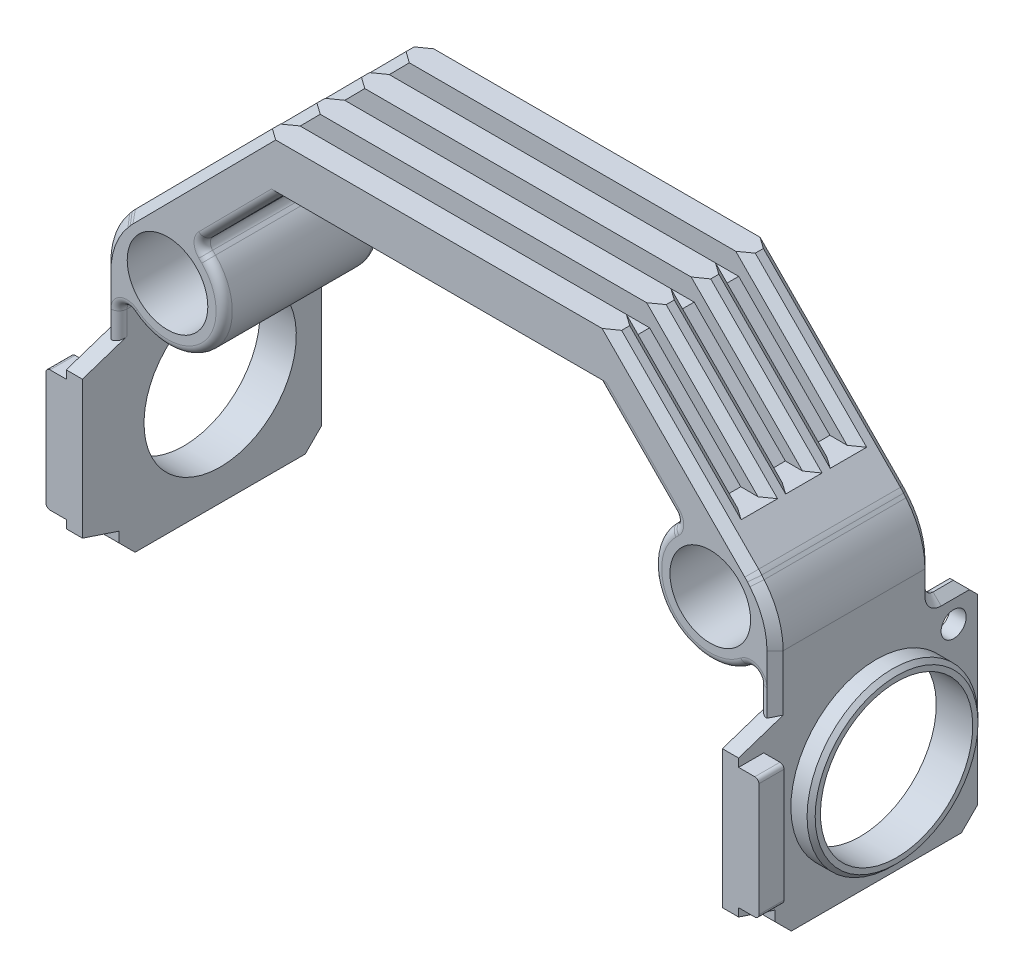
SolidWorks part; units mm, degrees
ref_plane "前视基准面" through (0, 0, 0) normal (0, 0, 1) x (1, 0, 0)
ref_plane "上视基准面" through (0, 0, 0) normal (0, 1, 0) x (1, 0, 0)
ref_plane "右视基准面" through (0, 0, 0) normal (1, 0, 0) x (0, 0, -1)
sketch "草图1" plane through (0, 0, 0) normal (0, 0, 1) x (1, 0, 0)
  circle A0 centre (-33.5, 0) radius 4.975
  circle A1 centre (-33.5, 0) radius 7
  point P4 (17.6304, -1.0507)
  dimension "D1" = 9.95
  dimension "D2" = 14
  dimension "D3" = 33.5
extrude "凸台-拉伸1" add sketch "草图1" along normal mid plane 25
sketch "草图3" plane through (0, 0, 0) normal (0, 0, 1) x (1, 0, 0)
  line L0 (-41.5, 1.356) -> (-41.5, -36.644)
  line L1 (-41.5, -36.644) -> (-39.5, -36.644)
  line L2 (-39.5, -36.644) -> (-39.5, -3.6056)
  line L3 (-41.5, 1.356) -> (-38.8623, 4.4995)
  circle A4 centre (-33.5, 0) radius 7 construction
  arc A5 (-38.8623, 4.4995) -> (-39.5, -3.6056) centre (-33.5, 0) ccw
  point P0 (-8, 1.7621)
  point P13 (-8, 0.2923)
  dimension "D1" = 8
  dimension "D2" = 2
  dimension "D3" = 38
  dimension "D4" = 40
extrude "凸台-拉伸2" add sketch "草图3" along normal mid plane 25
sketch "草图4" plane through (-41.5, 0, 0) normal (-1, 0, 0) x (0, 0, 1)
  circle A0 centre (0, -19.5) radius 9.4
  point P2 (0, 0)
  dimension "D1" = 18.8
  dimension "D2" = 19.5
extrude "切除-拉伸1" cut sketch "草图4" against normal through all
sketch "草图5" plane through (-41.5, 0, 0) normal (-1, 0, 0) x (0, 0, 1)
  circle A0 centre (0, -19.5) radius 10.55
  circle A1 centre (0, -19.5) radius 9.4
  circle A2 centre (0, -19.5) radius 9.4 construction
  dimension "D1" = 21.1
extrude "凸台-拉伸5" add sketch "草图5" along normal blind 2.5
chamfer "倒角3" distance 0.5 angle 45 1 edges at (-44, -30.05, 0)
sketch "草图6" plane through (-41.5, 0, 0) normal (-1, 0, 0) x (0, 0, 1)
  line L0 (12.5, -9.5) -> (17, -11)
  line L1 (12.5, 1.356) -> (12.5, -36.644) construction
  line L2 (17, -11) -> (17, -28)
  line L3 (17, -28) -> (12.5, -29.5)
  line L4 (12.5, -29.5) -> (12.5, -9.5)
  line L5 (0, -19.5) -> (17, -19.5) construction
  point P9 (12.5, -11)
  point P10 (12.5, -9.3792)
  point P11 (16.8715, -10.7591)
  point P12 (12.5, -32.9527)
  point P13 (12.5, -7.1943)
  dimension "D1" = 17
  dimension "D2" = 20
  dimension "D3" = 4.5
extrude "凸台-拉伸6" add sketch "草图6" against normal blind 2
sketch "草图7" plane through (-41.5, 0, 0) normal (-1, 0, 0) x (0, 0, 1)
  line L0 (17, -28) -> (17, -11) construction
  line L1 (13.9, -12) -> (17, -12)
  line L2 (13.9, -12) -> (13.9, -27)
  line L3 (13.9, -27) -> (17, -27)
  line L4 (17, -12) -> (17, -27)
  point P6 (17, -19.5)
  dimension "D1" = 15
  dimension "D2" = 3.1
extrude "凸台-拉伸7" add sketch "草图7" along normal blind 2.5
fillet "圆角1" radius 0.5 2 edges at (-44, -12, 15.45) (-44, -27, 15.45)
fillet "圆角2" radius 10 1 edges at (-41.5, 1.356, 0)
fillet "圆角3" radius 1 1 edges at (-39.5, -3.6056, 0)
sketch "草图8" plane through (0, 0, -12.5) normal (0, 0, -1) x (-1, 0, 0)
  line L0 (41.5, -2.2837) -> (41.5, -36.644) construction
  line L1 (41.5, -2.2837) -> (41.5, -6.245)
  line L2 (39.5, -6.245) -> (41.5, -6.245)
  line L3 (38.8623, 4.4995) -> (39.1604, 4.1442) construction
  line L4 (38.8623, 4.4995) -> (39.1604, 4.1442)
  arc A0 (38.8623, 4.4995) -> (37.875, -5.4644) centre (33.5, 0) ccw
  arc A1 (41.5, -2.2837) -> (39.1604, 4.1442) centre (31.5, -2.2837) ccw construction
  arc A2 (39.5, -6.245) -> (37.875, -5.4644) centre (38.5, -6.245) ccw construction
  arc A3 (41.5, -2.2837) -> (39.1604, 4.1442) centre (31.5, -2.2837) ccw
  arc A4 (39.5, -6.245) -> (37.875, -5.4644) centre (38.5, -6.245) ccw
  circle A5 centre (33.5, 0) radius 4.975 construction
extrude "切除-拉伸2" cut sketch "草图8" against normal blind 5.5
sketch "草图9" plane through (-41.5, 0, 0) normal (-1, 0, 0) x (0, 0, 1)
  line L0 (0, -19.5) -> (-12.5, -19.5) construction
  line L1 (-12.5, -6.245) -> (-12.5, -36.644) construction
  line L2 (-7, -6.245) -> (-12.5, -6.245) construction
  line L3 (-7, -6.245) -> (-12.5, -6.245) construction
  line L4 (-12.5, -32.755) -> (12.5, -32.755)
  line L5 (12.5, -29.5) -> (12.5, -36.644) construction
  line L6 (-12.5, -32.755) -> (-12.5, -36.644)
  line L7 (-12.5, -36.644) -> (12.5, -36.644)
  line L8 (12.5, -36.644) -> (12.5, -32.755)
extrude "切除-拉伸3" cut sketch "草图9" against normal through all
fillet "圆角4" radius 1 1 edges at (-40.5, -6.245, -7)
mirror "镜向2" about plane through (0, 0, 0) normal (1, 0, 0) of bodies 109
sketch "草图10" plane through (0, 0, -7) normal (0, 0, -1) x (-1, 0, 0)
  line L0 (-38.4723, 4.9271) -> (-21.5545, 22)
  line L1 (-21.5545, 22) -> (21.5545, 22)
  line L2 (21.5545, 22) -> (38.4723, 4.9271)
  line L3 (-31.1793, 6.6041) -> (-19.887, 18)
  line L4 (-19.887, 18) -> (19.887, 18)
  line L5 (19.887, 18) -> (31.1793, 6.6041)
  arc A1 (-37.875, -5.4644) -> (-38.8623, 4.4995) centre (-33.5, 0) ccw construction
  arc A2 (38.8623, 4.4995) -> (37.875, -5.4644) centre (33.5, 0) ccw construction
  arc A3 (38.4723, 4.9271) -> (31.1793, 6.6041) centre (33.5, 0) ccw
  arc A4 (-31.1793, 6.6041) -> (-38.4723, 4.9271) centre (-33.5, 0) ccw
  circle A5 centre (33.5, 0) radius 4.975 construction
  point P10 (0, 22)
  point P16 (0, 18)
  point P17 (-21.6674, 10.2957)
  dimension "D1" = 4
  dimension "D4" = 22
  dimension "D2" = 4
  dimension "D3" = 134.739
extrude "凸台-拉伸8" add sketch "草图10" against normal blind 3
pattern_linear "阵列(线性)1" count 4 spacing 5.5 along (0, 0, 1) of "凸台-拉伸8"
sketch "草图11" plane through (0, 0, -7) normal (0, 0, -1) x (-1, 0, 0)
  line L1 (-21.5545, 22) -> (-38.4723, 4.9271) construction
  line L2 (-38.4723, 4.9271) -> (-33.5452, 9.8994)
  line L3 (-33.5452, 9.8994) -> (-28.5729, 4.9723)
  line L4 (-38.4723, 4.9271) -> (-31.1793, 6.6041)
  arc A0 (-37.875, -5.4644) -> (-31.1793, 6.6041) centre (-33.5, 0) ccw construction
  arc A1 (-28.5729, 4.9723) -> (-31.1793, 6.6041) centre (-33.5, 0) ccw
  point P10 (-28.8352, 5.2191)
extrude "凸台-拉伸9" add sketch "草图11" against normal up to surface (19.5 mm away)
mirror "镜向3" about plane through (0, 0, 0) normal (1, 0, 0) of "凸台-拉伸9"
sketch "草图12" plane through (0, 0, -7) normal (0, 0, -1) x (-1, 0, 0)
  line L0 (-29.6384, 6.0281) -> (-19.2616, 16.5)
  line L1 (-28.5729, 4.9723) -> (-30.7039, 7.0839) construction
  line L2 (-19.2616, 16.5) -> (19.2616, 16.5)
  line L3 (19.2616, 16.5) -> (29.6384, 6.0281)
  line L4 (28.5729, 4.9723) -> (30.7039, 7.0839) construction
  line L6 (-19.887, 18) -> (19.887, 18) construction
  line L7 (-29.6384, 6.0281) -> (-31.7694, 8.1397)
  line L8 (-31.7694, 8.1397) -> (-20.5123, 19.5)
  line L9 (-20.5123, 19.5) -> (20.5123, 19.5)
  line L10 (20.5123, 19.5) -> (31.7694, 8.1397)
  line L11 (31.7694, 8.1397) -> (29.6384, 6.0281)
  dimension "D1" = 1.5
  dimension "D2" = 3
  dimension "D3" = 3
extrude "凸台-拉伸10" add sketch "草图12" against normal blind 19.5
chamfer "倒角5" distance 2 angle 45 6 edges at (-40.5, -6.245, -12.5) (-40.5, -32.755, -12.5) (-40.5, -32.755, 12.5) (40.5, -32.755, 12.5) (40.5, -6.245, -12.5) (40.5, -32.755, -12.5)
chamfer "倒角4" distance 1 angle 45 36 edges at (-40.8969, 1.1365, -7) (-38.6717, 4.7173, -7) (-39.0114, 4.3219, -7) (-39.0114, 4.3219, 12.5) (-41.5, -3.7643, -7) (-41.5, -6.245, -9.25) (-41.5, -5.9521, -7.2929) (27.5498, 15.9497, -4) (-30.0134, 13.4636, -7) (30.0134, 13.4636, -7) (38.6717, 4.7173, -7) (39.0114, 4.3219, -7) (39.0114, 4.3219, 12.5) (40.8969, 1.1365, 12.5) (40.8969, 1.1365, -7) (41.5, -3.7643, -7) (41.5, -5.8918, 12.5) (41.5, -6.245, -9.25) (41.5, -5.9521, -7.2929) (27.5498, 15.9497, 1.5) (27.5498, 15.9497, -1.5) (27.5498, 15.9497, 7) (27.5498, 15.9497, 4) (38.6717, 4.7173, 12.5) (-38.6717, 4.7173, 12.5) (30.0134, 13.4636, 12.5) (-30.0134, 13.4636, 12.5) (27.5498, 15.9497, 9.5) (-27.5498, 15.9497, 9.5) (-27.5498, 15.9497, 4) (-27.5498, 15.9497, 7) (-27.5498, 15.9497, -1.5) (-27.5498, 15.9497, 1.5) (-27.5498, 15.9497, -4) (-41.5, -5.8918, 12.5) (-40.8969, 1.1365, 12.5)
fillet "圆角6" radius 1 28 edges at (-38.1688, -5.3014, -7) (-39.397, -5.8029, -7.1701) (28.2744, -4.6576, 12.5) (38.1688, -5.3014, -7) (38.933, -5.3436, 12.5) (40, -9.5, 12.5) (39.5, -7.8725, 12.5) (39.397, -5.8029, -7.1701) (28.2744, -4.6576, -7) (29.1056, 5.5002, 12.5) (29.1056, 5.5002, -7) (-28.2744, -4.6576, -7) (-29.1056, 5.5002, -7) (-29.1056, 5.5002, 12.5) (29.6384, 6.0281, 2.75) (-24.45, 11.264, 12.5) (-29.6384, 6.0281, 2.75) (24.45, 11.264, 12.5) (24.45, 11.264, -7) (-24.45, 11.264, -7) (-39.5, -7.8725, 12.5) (-40, -9.5, 12.5) (-40, -6.245, -10.5) (40, -6.245, -10.5) (40, -6.245, -8) (-40, -6.245, -8) (-28.2744, -4.6576, 12.5) (-38.933, -5.3436, 12.5)
chamfer "倒角6" distance 2.5 angle 45 6 edges at (-33.5452, 9.8994, 8.25) (-33.5452, 9.8994, 2.75) (-33.5452, 9.8994, -2.75) (33.5452, 9.8994, -2.75) (33.5452, 9.8994, 2.75) (33.5452, 9.8994, 8.25)
sketch "草图14" plane through (0, 0, 0) normal (1, 0, 0) x (0, 0, -1)
  line L0 (0, -6) -> (0, -19.5) construction
  line L1 (0, -19.5) -> (9.5459, -9.9541) construction
  circle A0 centre (9.5459, -9.9541) radius 3 construction
  circle A1 centre (0, -19.5) radius 13.5 construction
  circle A2 centre (0, -19.5) radius 10.5 construction
  circle A3 centre (9.5459, -9.9541) radius 1.55
  dimension "D1" = 6
  dimension "D2" = 21
  dimension "D3" = 3.1
  dimension "D4" = 45
extrude "切除-拉伸4" cut sketch "草图14" against normal through all both and the other way through all
